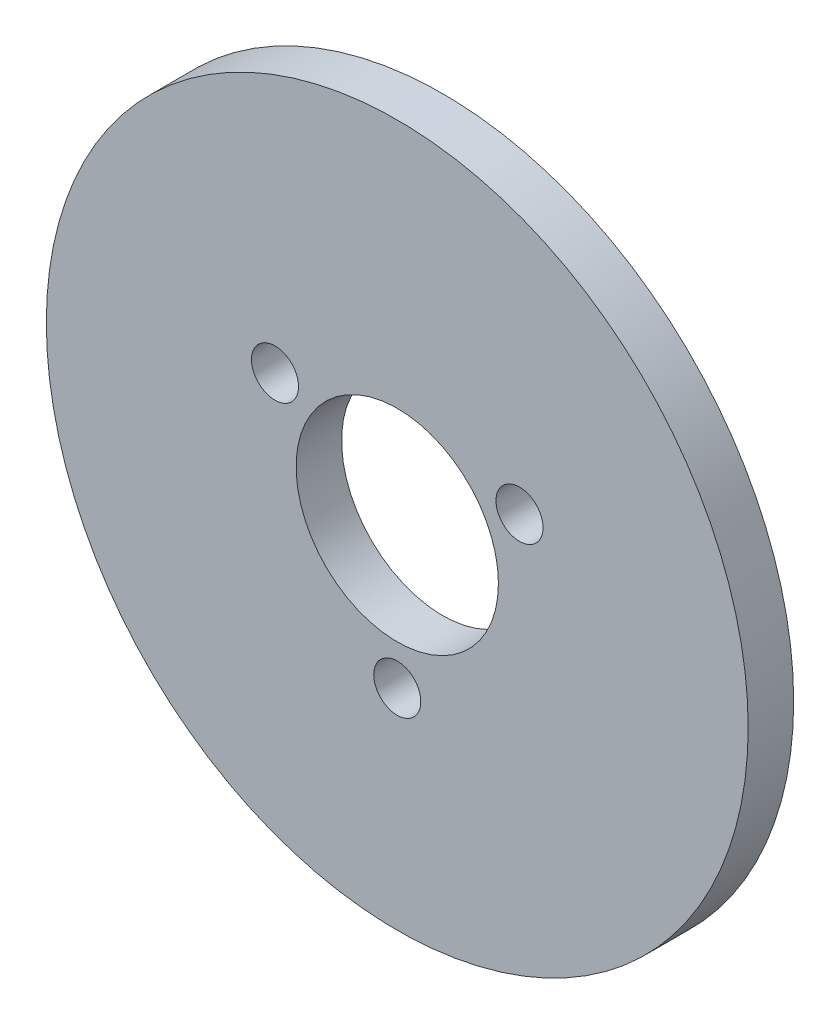
SolidWorks part; units mm, degrees
material "Acrylic (Medium-high impact)"
ref_plane "Front Plane" through (0, 0, 0) normal (0, 0, 1) x (1, 0, 0)
ref_plane "Top Plane" through (0, 0, 0) normal (0, 1, 0) x (1, 0, 0)
ref_plane "Right Plane" through (0, 0, 0) normal (1, 0, 0) x (0, 0, -1)
sketch "Sketch1" plane through (0, 0, 0) normal (0, 0, 1) x (1, 0, 0)
  circle A0 centre (0, 0) radius 22.375
  circle A1 centre (0, 0) radius 6.45
  dimension "D1" = 44.75
  dimension "D2" = 12.9
extrude "Boss-Extrude1" add sketch "Sketch1" along normal blind 2.9
sketch "Sketch2" plane through (0, 0, 0) normal (0, 0, -1) x (-1, 0, 0)
  circle A1 centre (7.7942, 4.5) radius 1.5
  circle A2 centre (7.7942, 4.5) radius 1.5
  circle A3 centre (-7.7942, 4.5) radius 1.5
  circle A4 centre (-7.7942, 4.5) radius 1.5
  circle A5 centre (0, -9) radius 1.5
  circle A6 centre (0, -9) radius 1.5
  dimension "D1" = 0
  dimension "D2" = 0
  dimension "D3" = 0
extrude "Cut-Extrude1" cut sketch "Sketch2" against normal through all
equation "\"smallPulleyTeeth\"= 15"
equation "\"largePulleyTeeth\"= 30"
equation "\"eighthThick\"= 2.9mm"
equation "\"sixteenthThick\" = 1.7mm"
equation "\"quarterThick\"=6.0mm"
equation "\"D1@Boss-Extrude1\"=\"eighthThick\""
